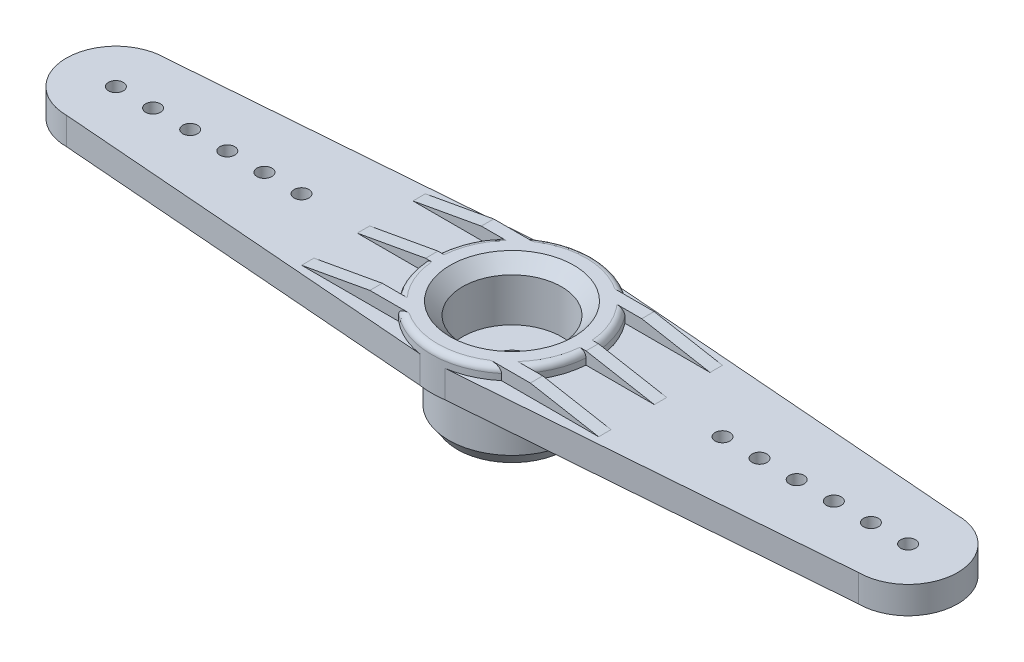
SolidWorks part; units mm, degrees
ref_plane "Спереди" through (0, 0, 0) normal (0, 0, 1) x (1, 0, 0)
ref_plane "Сверху" through (0, 0, 0) normal (0, 1, 0) x (1, 0, 0)
ref_plane "Справа" through (0, 0, 0) normal (1, 0, 0) x (0, 0, -1)
sketch "Эскиз1" plane through (0, 0, 0) normal (0, 1, 0) x (1, 0, 0)
  line L0 (-32, -4) -> (-1.0095, -6.4211)
  line L1 (-32, 4) -> (-1.0095, 6.4211)
  arc A0 (-1.0095, -6.4211) -> (-1.0095, 6.4211) centre (0, 0) ccw
  arc A1 (-32, 4) -> (-32, -4) centre (-32, 0) ccw
  circle A2 centre (-32, 0) radius 0.6
  circle A3 centre (-29, 0) radius 0.6
  circle A4 centre (-26, 0) radius 0.6
  circle A5 centre (-17, 0) radius 0.6
  circle A6 centre (-20, 0) radius 0.6
  circle A7 centre (-23, 0) radius 0.6
  circle A8 centre (0, 0) radius 1.5
extrude "Вытянуть2" add sketch "Эскиз1" along normal blind 8.2
sketch "Эскиз4" plane through (0, 0, 0) normal (0, -1, 0) x (1, 0, 0)
  line L4 (-32, 4.634) -> (0, 7.1582)
  line L5 (-32, -4.634) -> (0, -7.1582)
  circle A0 centre (0, 0) radius 5.1
  arc A1 (0, -7.1582) -> (0, 7.1582) centre (0, 0) ccw
  arc A2 (-32, 4.634) -> (-32, -4.634) centre (-32, 0) ccw
extrude "Вытянуть4" cut sketch "Эскиз4" against normal blind 5
sketch "Эскиз5" plane through (0, 0, 0) normal (0, -1, 0) x (1, 0, 0)
  circle A0 centre (0, 0) radius 3
extrude "Вытянуть5" cut sketch "Эскиз5" against normal blind 3
sketch "Эскиз6" plane through (0, 0, 0) normal (0, -1, 0) x (1, 0, 0)
  circle A0 centre (0, 0) radius 4
  circle A1 centre (0, 0) radius 3
extrude "Вытянуть6" cut sketch "Эскиз6" against normal blind 0.1
chamfer "Фаска1" distance 1 angle 35 1 edges at (0, 0, -5.1) first distance on face at (0, 5, -5.1)
sketch "Эскиз7" plane through (0, 8.2, 0) normal (0, 1, 0) x (1, 0, 0)
  line L1 (-32, 4) -> (-1.0095, 6.4211)
  line L2 (-32, -4) -> (-1.0095, -6.4211)
  arc A0 (-1.0095, 6.4211) -> (-1.0095, -6.4211) centre (0, 0) ccw
  arc A1 (-32, 4) -> (-32, -4) centre (-32, 0) ccw
extrude "Вытянуть7" cut sketch "Эскиз7" against normal blind 1
sketch "Эскиз8" plane through (0, 8.2, 0) normal (0, 1, 0) x (1, 0, 0)
  circle A0 centre (0, 0) radius 4
extrude "Вытянуть8" cut sketch "Эскиз8" against normal blind 4.5
sketch "Эскиз9" plane through (0, 5, 0) normal (0, -1, 0) x (1, 0, 0)
  line L0 (-8, 3.6) -> (-3.6125, 3.6)
  line L1 (-8, -3.6) -> (-3.6125, -3.6)
  line L2 (-8, 3.6) -> (-8, 4.6)
  line L3 (-8, 4.6) -> (-2.2023, 4.6)
  line L4 (-8, -3.6) -> (-8, -4.6)
  line L5 (-8, -4.6) -> (-2.2023, -4.6)
  arc A0 (-2.2023, 4.6) -> (-3.6125, 3.6) centre (0, 0) ccw
  arc A1 (-3.6125, -3.6) -> (-2.2023, -4.6) centre (0, 0) ccw
extrude "Вытянуть9" add sketch "Эскиз9" along normal blind 0.5
sketch "Эскиз10" plane through (0, 0, -4.6) normal (0, 0, -1) x (-1, 0, 0)
  line L0 (8, 4.5) -> (5.1011, 4.5)
  line L1 (8, 4.5) -> (2.2023, 4.5) construction
  line L2 (5.1011, 4.5) -> (8, 5)
  line L4 (8, 5) -> (8, 4.5)
extrude "Вытянуть11" cut sketch "Эскиз10" against normal through all
sketch "Эскиз11" plane through (0, 7.2, 0) normal (0, 1, 0) x (1, 0, 0)
  line L1 (-12, 0) -> (-12, 0.5)
  line L2 (-12, 0.5) -> (-6.4807, 0.5)
  line L3 (-12, 4) -> (-5.1235, 4)
  line L4 (-12, 4) -> (-12, 5)
  line L5 (-12, 5) -> (-4.1533, 5)
  line L6 (-12, -4) -> (-5.1235, -4)
  line L7 (-12, -4) -> (-12, -5)
  line L8 (-12, -5) -> (-4.1533, -5)
  line L9 (-12, 0) -> (-12, -0.5)
  line L10 (-12, -0.5) -> (-6.4807, -0.5)
  arc A0 (-4.1533, 5) -> (-5.1235, 4) centre (0, 0) ccw
  arc A1 (-6.4807, 0.5) -> (-6.4807, -0.5) centre (0, 0) ccw
  arc A2 (-5.1235, -4) -> (-4.1533, -5) centre (0, 0) ccw
extrude "Вытянуть12" add sketch "Эскиз11" along normal blind 1
sketch "Эскиз12" plane through (0, 0, 5) normal (0, 0, 1) x (1, 0, 0)
  line L0 (-6.4807, 8.2) -> (-12, 7.2)
  line L1 (-12, 8.2) -> (-12, 7.2) construction
  line L2 (-32, 7.2) -> (-1.0095, 7.2) construction
  line L3 (-12, 7.2) -> (-12, 8.2)
  line L4 (-12, 8.2) -> (-6.4807, 8.2)
extrude "Вытянуть13" cut sketch "Эскиз12" against normal through all
chamfer "Фаска2" distance 1 angle 45 1 edges at (0, 8.2, 4)
fillet "Скругление1" radius 0.5 3 edges at (-6.0603, 8.2, 2.3501) (-6.0603, 8.2, -2.3501) (6.5, 8.2, 0)
sketch "Эскиз13" plane through (0, 8.2, 0) normal (0, 1, 0) x (1, 0, 0)
  line L0 (0, 6.5) -> (0, -6.5)
  arc A0 (0, -6.5) -> (0, 6.5) centre (0, 0) ccw
extrude "Вытянуть14" cut sketch "Эскиз13" against normal through all
mirror "Зеркальное отражение1" about plane through (0, 0, -6.5) normal (-1, 0, 0) of bodies 114
